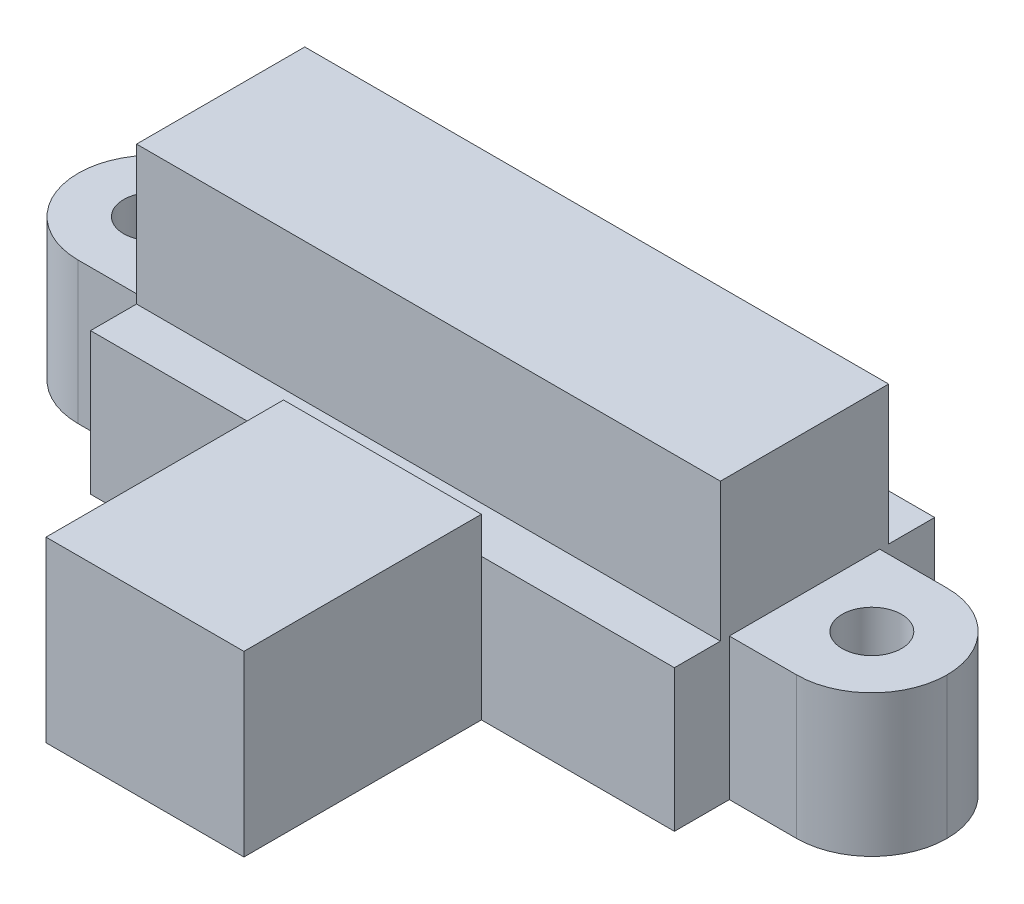
SolidWorks part; units mm, degrees
ref_plane "Front Plane" through (0, 0, 0) normal (0, 0, 1) x (1, 0, 0)
ref_plane "Top Plane" through (0, 0, 0) normal (0, 1, 0) x (1, 0, 0)
ref_plane "Right Plane" through (0, 0, 0) normal (1, 0, 0) x (0, 0, -1)
sketch "Sketch1" plane through (0, 0, 0) normal (0, 1, 0) x (1, 0, 0)
  line L0 (21.95, -3.8) -> (14.75, -3.8)
  line L1 (-14.75, -6.575) -> (14.75, -6.575)
  line L2 (-14.75, 6.575) -> (-14.75, 3.8)
  line L3 (-14.75, 6.575) -> (14.75, 6.575)
  line L4 (-14.75, -3.8) -> (-14.75, -6.575)
  line L5 (-14.75, -6.575) -> (14.75, 6.575) construction
  line L6 (-14.75, 6.575) -> (14.75, -6.575) construction
  line L7 (-21.95, -3.8) -> (-14.75, -3.8)
  line L8 (-21.95, -3.8) -> (-21.95, 3.8)
  line L9 (-21.95, 3.8) -> (-14.75, 3.8)
  line L10 (14.75, -6.575) -> (14.75, -3.8)
  line L15 (14.75, 6.575) -> (14.75, 3.8)
  line L19 (21.95, -3.8) -> (21.95, 3.8)
  line L21 (14.75, 3.8) -> (21.95, 3.8)
  point P0 (0, 0)
  dimension "D1" = 29.5
  dimension "D2" = 13.15
  dimension "D3" = 7.2
  dimension "D4" = 7.6
extrude "Boss-Extrude1" add sketch "Sketch1" along normal blind 7.16
fillet "Fillet2" radius 3.8 1 edges at (-21.95, 3.58, -3.8) type face fillet first side face at (-21.95, 3.58, 0) second side face at (-18.35, 3.58, -3.8)
fillet "Fillet3" radius 3.8 1 edges at (-21.95, 3.58, 3.8) type face fillet first side face at (-21.95, 3.58, 1.9) second side face at (-18.35, 3.58, 3.8)
fillet "Fillet4" radius 3.8 1 edges at (21.95, 3.58, -3.8) type face fillet first side face at (21.95, 3.58, 0) second side face at (18.35, 3.58, -3.8)
fillet "Fillet5" radius 3.8 1 edges at (21.95, 3.58, 3.8) type face fillet first side face at (18.35, 3.58, 3.8) second side face at (21.95, 3.58, 1.9)
sketch "Sketch2" plane through (0, 7.16, 0) normal (0, 1, 0) x (1, 0, 0)
  line L0 (14.75, 3.8) -> (14.75, 6.575) construction
  line L1 (-14.75, -4.25) -> (14.75, -4.25)
  line L2 (-14.75, -4.25) -> (-14.75, 4.25)
  line L3 (-14.75, 4.25) -> (14.75, 4.25)
  line L4 (14.75, -4.25) -> (14.75, 4.25)
  line L5 (-14.75, -4.25) -> (14.75, 4.25) construction
  line L6 (-14.75, 4.25) -> (14.75, -4.25) construction
  point P0 (0, 0)
  dimension "D1" = 8.5
extrude "Boss-Extrude2" add sketch "Sketch2" along normal blind 7
sketch "Sketch3" plane through (0, 0, 6.575) normal (0, 0, 1) x (1, 0, 0)
  line L0 (-5, 0) -> (-5, 9)
  line L1 (-14.75, 0) -> (14.75, 0) construction
  line L2 (5, 0) -> (5, 9)
  line L3 (5, 9) -> (-5, 9)
  line L9 (-14.75, 0) -> (14.75, 0)
  line L10 (14.75, 0) -> (14.75, 7.16)
  line L11 (14.75, 7.16) -> (-14.75, 7.16)
  line L12 (-14.75, 7.16) -> (-14.75, 0)
  line L13 (-5, 0) -> (5, 0)
  dimension "D1" = 9
  dimension "D4" = 0
extrude "Boss-Extrude4" add sketch "Sketch3" along normal blind 12 separate body
sketch "Sketch4" plane through (0, 7.16, 0) normal (0, 1, 0) x (1, 0, 0)
  circle A0 centre (-18.15, 0) radius 1.5
  circle A1 centre (18.15, 0) radius 1.5
  dimension "D1" = 3
  dimension "D2" = 3
extrude "Cut-Extrude1" cut sketch "Sketch4" against normal blind 9
